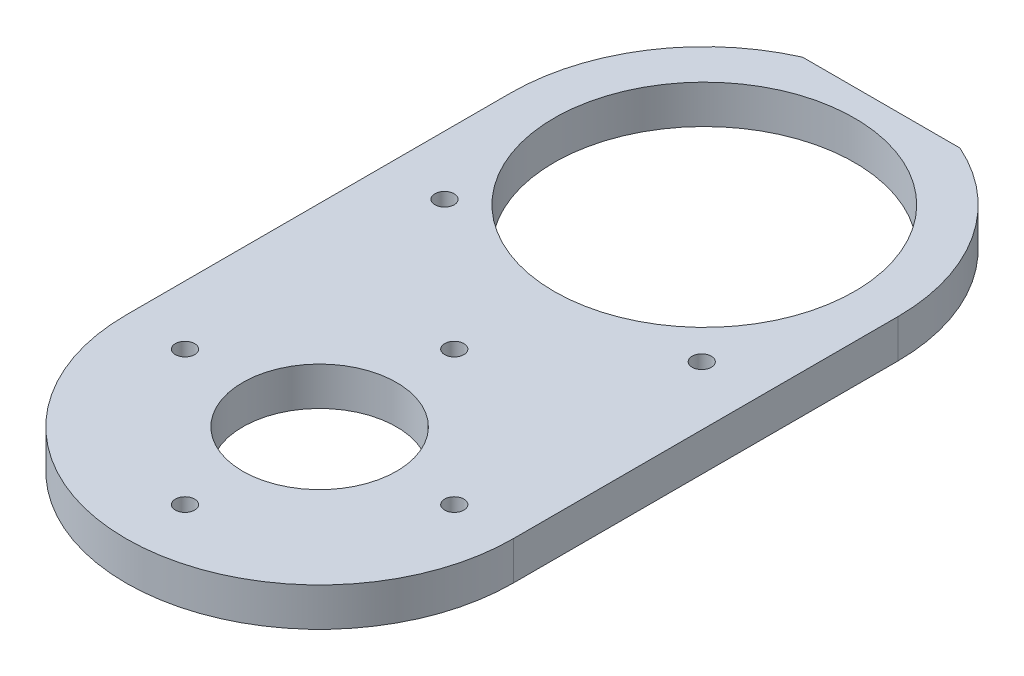
SolidWorks part; units mm, degrees
ref_plane "Front Plane" through (0, 0, 0) normal (0, 0, 1) x (1, 0, 0)
ref_plane "Top Plane" through (0, 0, 0) normal (0, 1, 0) x (1, 0, 0)
ref_plane "Right Plane" through (0, 0, 0) normal (1, 0, 0) x (0, 0, -1)
sketch "Sketch1" plane through (0, 0, 0) normal (0, 1, 0) x (1, 0, 0)
  line L0 (0, 0) -> (0, -127) construction
  line L1 (63.881, 0) -> (63.881, -127)
  line L2 (-63.881, 0) -> (-63.881, -127)
  line L3 (74.4454, 35.8679) -> (68.7606, 48.3222)
  line L4 (-48.26, 0) -> (-63.881, 0) construction
  line L5 (48.26, 0) -> (63.881, 0) construction
  line L6 (62.7955, 11.7263) -> (81.5561, 20.2895)
  line L7 (50, 39.759) -> (68.7606, 48.3222)
  line L8 (81.5561, 20.2895) -> (75.8713, 32.7439)
  line L9 (0, 48.26) -> (0, 58.42) construction
  line L10 (74.4454, 35.8679) -> (43.162, 21.5886)
  line L11 (75.8713, 32.7439) -> (44.5879, 18.4647)
  line L12 (0, 58.42) -> (25.8435, 58.42)
  line L13 (0, 58.42) -> (-25.8435, 58.42)
  arc A0 (43.162, 21.5886) -> (44.5879, 18.4647) centre (0, 0) ccw
  circle A1 centre (0, -127) radius 25.4
  arc A2 (63.881, 0) -> (62.7955, 11.7263) centre (0, 0) ccw
  arc A3 (-63.881, -127) -> (63.881, -127) centre (0, -127) ccw
  circle A4 centre (0, -127) radius 50.8 construction
  arc A5 (50, 39.759) -> (25.8435, 58.42) centre (0, 0) ccw
  arc A6 (-25.8435, 58.42) -> (-63.881, 0) centre (0, 0) ccw
  point P6 (0, -63.5)
  point P12 (-56.0705, 0)
  point P13 (56.0705, 0)
  dimension "D1" = 15.621
  dimension "D3" = 10.16
  dimension "D2" = 15.621
  dimension "D4" = 25.8435
  dimension "D5" = 25.8435
  dimension "D6" = 127.762
sketch "Sketch2" plane through (0, 0, 0) normal (0, 1, 0) x (1, 0, 0)
  arc A0 (63.881, 0) -> (62.7955, 11.7263) centre (0, 0) ccw construction
  arc A1 (-63.881, -127) -> (63.881, -127) centre (0, -127) ccw construction
  point P0 (63.609, 5.8882)
  point P1 (0, -190.881)
  dimension "D1" = 206.7952
ref_plane "Plane2" through (0, 0, 63.5) normal (0, 0, -1) x (-1, 0, 0)
sketch "Sketch3" plane through (0, 0, 0) normal (0, -1, 0) x (1, 0, 0)
  line L0 (48.26, 0) -> (63.881, 0) construction
  line L1 (63.881, 0) -> (-48.26, 0) construction
  line L2 (-48.26, 0) -> (-63.881, 0) construction
  arc A1 (44.5879, -18.4647) -> (43.162, -21.5886) centre (0, 0) ccw construction
  circle A2 centre (-56.0705, 0) radius 3.175
  circle A3 centre (56.0705, 0) radius 3.175
  dimension "D1" = 15.621
  dimension "D2" = 112.141
  dimension "D3" = 15.621
extrude "Cut-Extrude1" cut sketch "Sketch3" against normal blind 6.35 rebuild error yes
mirror "Mirror1" about plane through (0, 0, 63.5) normal (0, 0, -1) rebuild error yes
sketch "Sketch4" plane through (0, 0, 0) normal (0, 1, 0) x (1, 0, 0)
  line L0 (0, -127) -> (0, 0) construction
  line L1 (-63.9347, -127) -> (-63.9347, 0)
  line L2 (63.9347, -127) -> (63.9347, 0)
  line L3 (-15.5469, 56.1656) -> (15.5469, 56.1656)
  line L4 (-59.8707, -127) -> (-59.8707, 0)
  line L5 (59.8707, -127) -> (59.8707, 0)
  line L6 (-54.0287, -127) -> (-54.0287, 0)
  line L7 (54.0287, -127) -> (54.0287, 0)
  line L8 (0, -127) -> (-44.45, -127) construction
  line L9 (-44.45, -127) -> (44.45, -127) construction
  line L10 (44.45, -127) -> (0, -127) construction
  line L11 (0, -127) -> (0, -171.45) construction
  line L12 (0, -171.45) -> (0, -82.55) construction
  line L13 (0, 0) -> (44.45, -45.3064) construction
  line L14 (44.45, -45.3064) -> (-44.45, -41.3113) construction
  line L15 (-25.976, 58.42) -> (25.976, 58.42)
  line L16 (-13.6268, 50.5776) -> (13.6268, 50.5776)
  line L17 (-25.976, 50.5776) -> (26.5066, 50.5776) construction
  line L18 (-25.976, 56.1656) -> (26.5066, 56.1656) construction
  arc A0 (-63.9347, -127) -> (63.9347, -127) centre (0, -127) ccw
  arc A1 (63.9347, 0) -> (25.976, 58.42) centre (0, 0) ccw
  circle A2 centre (0, -127) radius 25.4
  circle A3 centre (0, 0) radius 49.5875
  arc A4 (59.8707, 0) -> (27.0028, 53.4355) centre (0, 0) ccw
  arc A5 (-59.8707, -127) -> (59.8707, -127) centre (0, -127) ccw
  arc A6 (54.0287, 0) -> (25.7168, 47.5157) centre (0, 0) ccw
  arc A7 (-54.0287, -127) -> (54.0287, -127) centre (0, -127) ccw
  circle A8 centre (0, -171.45) radius 3.175
  circle A9 centre (-44.45, -127) radius 3.175
  circle A10 centre (44.45, -127) radius 3.175
  circle A11 centre (0, -82.55) radius 3.175
  circle A12 centre (-44.45, -41.3113) radius 3.175
  circle A13 centre (44.45, -45.3064) radius 3.175
  arc A14 (-25.7168, 47.5157) -> (-54.0287, 0) centre (0, 0) ccw
  arc A15 (54.0287, 0) -> (-54.0287, 0) centre (0, 0) ccw construction
  arc A16 (-27.0028, 53.4355) -> (-59.8707, 0) centre (0, 0) ccw
  arc A17 (59.8707, 0) -> (-59.8707, 0) centre (0, 0) ccw construction
  arc A18 (-25.976, 58.42) -> (-63.9347, 0) centre (0, 0) ccw
  arc A19 (63.9347, 0) -> (-63.9347, 0) centre (0, 0) ccw construction
  arc A20 (15.5469, 56.1656) -> (27.0028, 53.4355) centre (15.5469, 30.7656) cw
  arc A21 (25.7168, 47.5157) -> (13.6268, 50.5776) centre (13.6268, 25.1776) ccw
  arc A22 (-15.5469, 56.1656) -> (-27.0028, 53.4355) centre (-15.5469, 30.7656) ccw
  arc A23 (-25.7168, 47.5157) -> (-13.6268, 50.5776) centre (-13.6268, 25.1776) cw
  point P4 (0, -63.5)
  dimension "D2" = 4.064
  dimension "D1" = 25.4
  dimension "D4" = 44.45
  dimension "D5" = 63.4703
  dimension "D6" = 44.45
  dimension "D7" = 44.45
  dimension "D8" = 88.9897
  dimension "D3" = 9.906
extrude "Boss-Extrude4" add sketch "Sketch4" along normal blind 12.7 separate body contours A18 L1 A0 L2 A1 L15
extrude "Cut-Extrude3" cut sketch "Sketch4<5>" along normal blind 5.588 contours L3 A22 A16 L4 A5 L5 A4 A20 A14 A23 L16 A21 A6 L7 A7 L6 region at (0, 0, -53.4563)
sketch "Sketch4<5>" plane through (0, 0, 0) normal (0, 1, 0) x (1, 0, 0) same geometry as "Sketch4"
extrude "Cut-Extrude4" cut sketch "Sketch4<6>" along normal up to surface (12.7 mm away) contours A3 | A2 region at (0, 0, 127) region at (0, 0, 0) up to face at (0, 12.7, 31.641)
sketch "Sketch4<6>" plane through (0, 0, 0) normal (0, 1, 0) x (1, 0, 0) same geometry as "Sketch4"
extrude "Cut-Extrude8" cut sketch "Sketch4<8>" against normal blind 6.35 from surface contours A10 | A8 | A9 | A11 | A13 | A12 starting at face at (0, 12.7, 49.5875)
sketch "Sketch4<8>" plane through (0, 0, 0) normal (0, 1, 0) x (1, 0, 0) same geometry as "Sketch4"
